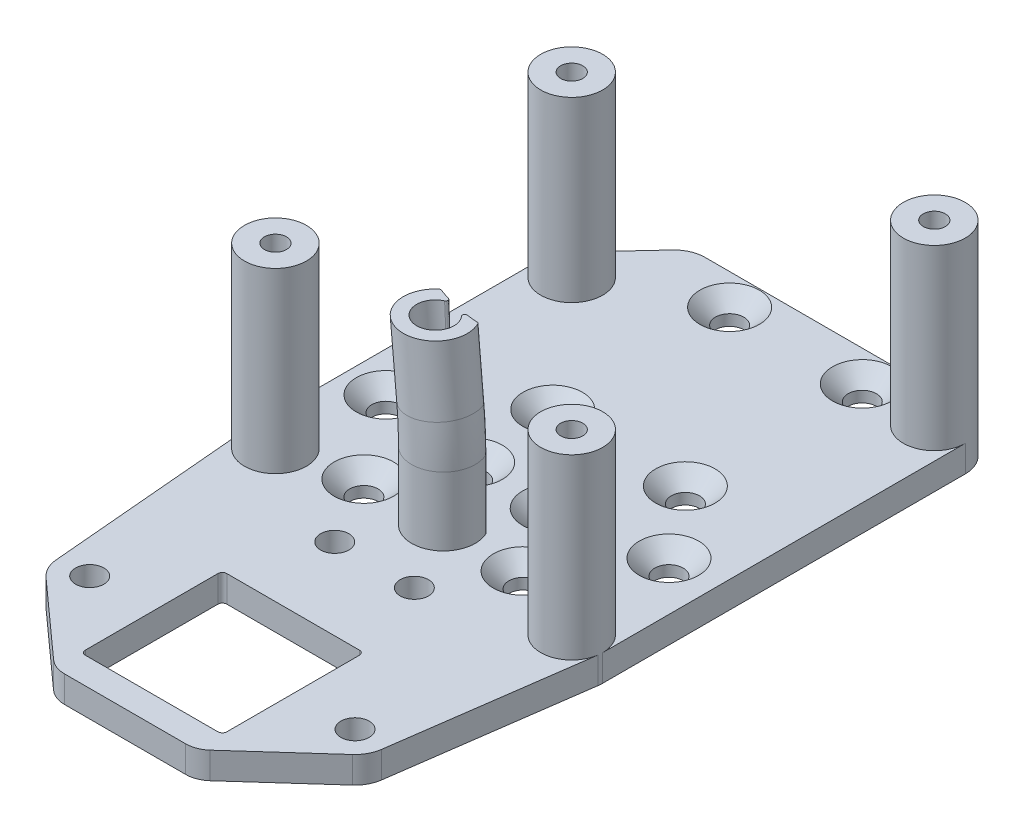
SolidWorks part; units mm, degrees
material "6061-T6 (SS)"
ref_plane "Front Plane" through (0, 0, 0) normal (0, 0, 1) x (1, 0, 0)
ref_plane "Top Plane" through (0, 0, 0) normal (0, 1, 0) x (1, 0, 0)
ref_plane "Right Plane" through (0, 0, 0) normal (1, 0, 0) x (0, 0, -1)
sketch "Hole Locations" plane through (0, 0, 0) normal (0, 1, 0) x (1, 0, 0)
  line L0 (0, 0) -> (0, 3.5) construction
  line L1 (0, 0) -> (0, 41) construction
  line L2 (0, 3.5) -> (-18, 3.5) construction
  line L3 (-14.64, 24.83) -> (-14.64, 23.33) construction
  line L4 (3.56, 24.83) -> (3.56, 23.33) construction
  line L5 (-32.84, 24.83) -> (-32.84, 23.33) construction
  circle A0 centre (-18, 3.5) radius 12.7 construction
  circle A1 centre (-18, 3.5) radius 9 construction
  arc A2 (3.56, 24.83) -> (-32.84, 24.83) centre (-14.64, 24.83) ccw construction
  arc A3 (-32.84, 23.33) -> (3.56, 23.33) centre (-14.64, 23.33) ccw construction
  point P3 (0, 41)
  point P8 (-35, 35)
  point P12 (-14.64, 24.08)
  point P17 (-35, 1.5)
  dimension "D5" = 25.4
  dimension "D6" = 18
  dimension "D10" = 18.2
  dimension "D11" = 35
  dimension "D2" = 3.5
  dimension "D3" = 41
  dimension "D4" = 18
  dimension "D7" = 3.36
  dimension "D8" = 20.58
  dimension "D9" = 1.5
  dimension "D12" = 1.5
  dimension "D13" = 35
sketch "Sketch2" plane through (0, 0, 0) normal (0, 1, 0) x (1, 0, 0)
  line L1 (-85.0501, -47.0767) -> (20.8074, -47.0767)
  line L2 (-85.0501, -47.0767) -> (-85.0501, 53.3551)
  line L3 (-85.0501, 53.3551) -> (20.8074, 53.3551)
  line L4 (20.8074, -47.0767) -> (20.8074, 53.3551)
extrude "Boss-Extrude1" add sketch "Sketch2" along normal blind 3
hole_wizard "Ø4.2 (4.2) Diameter Hole1" positions "Sketch5" profile "Sketch6" hole size "Ø4.2" standard "ANSI Metric" end condition up to next
sketch "Sketch5" plane through (0, 3, 0) normal (0, 1, 0) x (1, 0, 0)
  point P0 (-18, 3.5)
sketch "Sketch6" plane through (-18, 3, -3.5) normal (1, 0, 0) x (0, 0, 1)
  line L0 (0, 0) -> (0, 3)
  line L1 (0, 3) -> (2.1, 3)
  line L2 (2.1, 3) -> (2.1, 0)
  line L5 (2.1, 0) -> (0, 0)
  line L11 (0, -6.35) -> (0, 107.95) construction
  dimension "Thru Hole Dia." = 4.2
  dimension "Thru Hole Depth" = 3
sketch "Sketch7" plane through (0, 3, 0) normal (0, 1, 0) x (1, 0, 0)
  circle A0 centre (-35, 1.5) radius 3.5
  circle A1 centre (0, 41) radius 3.5
  circle A2 centre (0, 0) radius 3.5
  circle A3 centre (-35, 35) radius 3.5
  dimension "D1" = 7
extrude "Boss-Extrude2" add sketch "Sketch7" along normal blind 20.1
hole_wizard "Tap Drill for M3x0.5 Tap1" positions "Sketch8" profile "Sketch9" hole size "M3x0.5" standard "ANSI Metric" end condition up to next
sketch "Sketch8" plane through (0, 23.1, 0) normal (0, 1, 0) x (1, 0, 0)
  point P0 (-35, 1.5)
  point P3 (0, 41)
  point P6 (0, 0)
  point P9 (-35, 35)
sketch "Sketch9" plane through (-35, 23.1, -1.5) normal (1, 0, 0) x (0, 0, 1)
  line L0 (0, 0) -> (0, 23.1)
  line L1 (0, 23.1) -> (1.25, 23.1)
  line L2 (1.25, 23.1) -> (1.25, 0)
  line L5 (1.25, 0) -> (0, 0)
  line L11 (0, -6.35) -> (0, 107.95) construction
  dimension "Thru Hole Dia." = 2.5
  dimension "Thru Hole Depth" = 23.1
sketch "Chube Hole Positions" plane through (0, 3, 0) normal (0, 1, 0) x (1, 0, 0)
  line L0 (-18, 3.5) -> (-27, 3.5) construction
  circle A0 centre (-18, 3.5) radius 9 construction
  point P3 (-27, 3.5)
  point P4 (-22.5, 11.2942)
  point P7 (-13.5, 11.2942)
  point P8 (-9, 3.5)
  point P9 (-13.5, -4.2942)
  point P10 (-22.5, -4.2942)
  dimension "D3" = 9
  dimension "D2" = 6
hole_wizard "CSK for M3 SFHCS1" positions "Sketch15" profile "Sketch16" countersink size "M3" standard "ANSI Metric" end condition up to next
sketch "Sketch15" plane through (0, 3, 0) normal (0, 1, 0) x (1, 0, 0)
  point P24 (-22.5, 11.2942)
  point P27 (-13.5, 11.2942)
  point P30 (-9, 3.5)
  point P34 (-27, 3.5)
sketch "Sketch16" plane through (-22.5, 3, -11.2942) normal (1, 0, 0) x (0, 0, 1)
  line L0 (0, 0) -> (0, 3)
  line L1 (0, 3) -> (1.6, 3)
  line L2 (1.6, 3) -> (1.6, 1.76)
  line L3 (1.6, 1.76) -> (3.36, 0)
  line L5 (3.36, 0) -> (0, 0)
  line L6 (-1.6, 1.76) -> (-3.36, 0) construction
  line L11 (0, -6.35) -> (0, 107.95) construction
  dimension "Thru Hole Dia." = 3.2
  dimension "Thru Hole Depth" = 3
  dimension "Near C'Sink Dia." = 6.72
  dimension "Near C'Sink Angle" = 90
hole_wizard "M3 Clearance Hole1" positions "Sketch31" profile "Sketch32" hole size "M3" standard "ANSI Metric" end condition up to next
sketch "Sketch31" plane through (0, 3, 0) normal (0, 1, 0) x (1, 0, 0)
  circle A0 centre (-18, 3.5) radius 9 construction
  point P3 (-22.5, -4.2942)
  point P6 (-13.5, -4.2942)
sketch "Sketch32" plane through (-22.5, 3, 4.2942) normal (1, 0, 0) x (0, 0, 1)
  line L0 (0, 0) -> (0, 3)
  line L1 (0, 3) -> (1.6, 3)
  line L2 (1.6, 3) -> (1.6, 0)
  line L5 (1.6, 0) -> (0, 0)
  line L11 (0, -6.35) -> (0, 107.95) construction
  dimension "Thru Hole Dia." = 3.2
  dimension "Thru Hole Depth" = 3
sketch "MGN12 Hole Positions" plane through (0, 3, 0) normal (0, 1, 0) x (1, 0, 0)
  line L0 (-18, 3.5) -> (-13.29, 3.5) construction
  line L1 (0, 3.5) -> (-18, 3.5) construction
  line L2 (-15.645, 3.5) -> (-15.645, 31) construction
  line L4 (1.855, 17.5) -> (-33.145, 17.5)
  line L5 (1.855, 17.5) -> (1.855, 44.5)
  line L6 (1.855, 44.5) -> (-33.145, 44.5)
  line L7 (-33.145, 17.5) -> (-33.145, 44.5)
  line L8 (1.855, 17.5) -> (-33.145, 44.5) construction
  line L9 (1.855, 44.5) -> (-33.145, 17.5) construction
  line L10 (-8.145, 21) -> (-23.145, 21)
  line L11 (-8.145, 21) -> (-8.145, 41)
  line L12 (-8.145, 41) -> (-23.145, 41)
  line L13 (-23.145, 21) -> (-23.145, 41)
  line L14 (-8.145, 21) -> (-23.145, 41) construction
  line L15 (-8.145, 41) -> (-23.145, 21) construction
  circle A0 centre (0, 41) radius 3.5 construction
  dimension "D1" = 4.71
  dimension "D2" = 35
  dimension "D3" = 27
  dimension "D4" = 20
  dimension "D5" = 15
hole_wizard "CSK for M3 SFHCS2" positions "Sketch18" profile "Sketch19" countersink size "M3" standard "ANSI Metric" end condition up to next
sketch "Sketch18" plane through (0, 3, 0) normal (0, 1, 0) x (1, 0, 0)
  point P0 (-23.145, 41)
  point P3 (-8.145, 41)
  point P6 (-8.145, 21)
  point P9 (-23.145, 21)
sketch "Sketch19" plane through (-23.145, 3, -41) normal (1, 0, 0) x (0, 0, 1)
  line L0 (0, 0) -> (0, 3)
  line L1 (0, 3) -> (1.6, 3)
  line L2 (1.6, 3) -> (1.6, 1.76)
  line L3 (1.6, 1.76) -> (3.36, 0)
  line L5 (3.36, 0) -> (0, 0)
  line L6 (-1.6, 1.76) -> (-3.36, 0) construction
  line L11 (0, -6.35) -> (0, 107.95) construction
  dimension "Thru Hole Dia." = 3.2
  dimension "Thru Hole Depth" = 3
  dimension "Near C'Sink Dia." = 6.72
  dimension "Near C'Sink Angle" = 90
ref_plane "Plane1" through (0, 0, -3.5) normal (0, 0, 1) x (1, 0, 0)
sketch "Sketch20" plane through (0, 0, -3.5) normal (0, 0, 1) x (1, 0, 0)
  line L0 (-18, 3) -> (-18, 10.7231)
  line L2 (-18.2074, 15.2721) -> (-19.0139, 24.1)
  line L3 (-68, 10.7231) -> (-18.0519, 13) construction
  line L4 (-85.0501, 3) -> (20.8074, 3) construction
  line L6 (-31.5, 23.1) -> (-38.5, 23.1) construction
  arc A0 (-18, 10.7231) -> (-18.2074, 15.2721) centre (-68, 10.7231) ccw
  dimension "D1" = 10
  dimension "D2" = 50
  dimension "D3" = 95.22
  dimension "D4" = 1
sketch "Sketch26" plane through (0, 3, 0) normal (0, 1, 0) x (1, 0, 0)
  line L0 (-33, -21.5) -> (-3, -21.5) construction
  line L3 (-10, -29.5) -> (-26, -29.5)
  line L4 (-10, -29.5) -> (-10, -13.5)
  line L5 (-10, -13.5) -> (-26, -13.5)
  line L6 (-26, -29.5) -> (-26, -13.5)
  line L7 (-10, -29.5) -> (-26, -13.5) construction
  line L8 (-10, -13.5) -> (-26, -29.5) construction
  circle A0 centre (-18, -21.5) radius 8 construction
  circle A2 centre (-18, -21.5) radius 11 construction
  circle A3 centre (-33, -21.5) radius 3.5 construction
  circle A4 centre (-3, -21.5) radius 3.5 construction
  point P3 (-29, -21.5)
  point P5 (-18, 3.5)
  point P8 (-18, -21.5)
  dimension "D1" = 16
  dimension "D2" = 3
  dimension "D4" = 7
  dimension "D3" = 4
  dimension "D5" = 25
  dimension "D6" = 16
extrude "CPAP Hole" cut sketch "Sketch26" against normal up to surface (3 mm away) up to face at (-23.145, 0, -42.6)
hole_wizard "M3 Clearance Hole2" positions "Sketch27" profile "Sketch28" hole size "M3" standard "ANSI Metric" end condition up to next
sketch "Sketch27" plane through (0, 3, 0) normal (0, 1, 0) x (1, 0, 0)
  point P0 (-3, -21.5)
  point P14 (-33, -21.5)
sketch "Sketch28" plane through (-3, 3, 21.5) normal (1, 0, 0) x (0, 0, 1)
  line L0 (0, 0) -> (0, 3)
  line L1 (0, 3) -> (1.6, 3)
  line L2 (1.6, 3) -> (1.6, 0)
  line L5 (1.6, 0) -> (0, 0)
  line L11 (0, -6.35) -> (0, 107.95) construction
  dimension "Thru Hole Dia." = 3.2
  dimension "Thru Hole Depth" = 3
sketch "Sketch21" plane through (0, 3, 0) normal (0, 1, 0) x (1, 0, 0)
  circle A0 centre (-18, 3.5) radius 2.1 construction
  circle A1 centre (-18, 3.5) radius 2.1
  circle A2 centre (-18, 3.5) radius 3.6
  dimension "D1" = 1.5
sweep "Sweep1" add profiles "Sketch21" path "Sketch20"
sketch "Sketch23" plane through (0, 0, 47.0767) normal (0, 0, 1) x (1, 0, 0)
  line L1 (-38.5, 23.1) -> (3.5, 23.1)
  line L2 (-38.5, 23.1) -> (-38.5, 24.4275)
  line L3 (-38.5, 24.4275) -> (3.5, 24.4275)
  line L4 (3.5, 23.1) -> (3.5, 24.4275)
extrude "Cut-Extrude1" cut sketch "Sketch23" against normal through all
sketch "Sketch25" plane through (0, 3, 0) normal (0, 1, 0) x (1, 0, 0)
  line L0 (-14.64, 24.83) -> (-14.64, 23.33) construction
  line L1 (3.56, 24.83) -> (3.56, 23.33)
  line L2 (-32.84, 24.83) -> (-32.84, 23.33)
  arc A0 (3.56, 24.83) -> (-32.84, 24.83) centre (-14.64, 24.83) ccw
  arc A1 (-32.84, 23.33) -> (3.56, 23.33) centre (-14.64, 23.33) ccw
  circle A2 centre (-18, 3.5) radius 3.6 construction
  point P2 (-14.64, 24.08)
  dimension "D1" = 20.58
  dimension "D3" = 18.2
  dimension "D2" = 3.36
  dimension "D4" = 1.5
extrude "Cut-Extrude3" cut sketch "Sketch25" along normal up to surface (20.1 mm away) up to face at (-22.5375, 23.1, -3.5)
fillet "Fillet1" radius 0.25 12 edges at (-20.6472, 15.195, -6.15) (-17.5822, 18.9453, -5.3694) (-16.8679, 11.266, -5.2669) (-18.729, 19.4348, -5.5953) (-18.579, 14.9229, -5.5614) (-14.7905, 6.8616, -5.1306) (-20.4932, 6.8616, -6.0969) (-16.8644, 6.8616, -5.2664) (-18.4904, 6.8616, -5.5419)
sketch "Sketch29" plane through (0, 3, 0) normal (0, 1, 0) x (1, 0, 0)
  line L3 (3.5, 0) -> (3.5, 41)
  line L4 (0, 44.5) -> (-29.4219, 44.5)
  line L5 (-31.9852, 43.3831) -> (-37.5633, 37.3831)
  line L13 (-38.5, 35) -> (-38.5, 1.5)
  line L16 (-10, -32.5) -> (-26, -32.5)
  line L21 (-10, -32.5) -> (-26, -32.5)
  line L22 (-36.4868, -21.8032) -> (-38.4868, 1.1968)
  line L23 (-26, -32.5) -> (-35.34, -24.1027)
  line L24 (0.4664, -21.9837) -> (3.4664, -0.4837)
  line L25 (-10, -32.5) -> (-0.66, -24.1027)
  circle A0 centre (-33, -21.5) radius 3.5 construction
  arc A1 (-36.4868, -21.8032) -> (-35.34, -24.1027) centre (-33, -21.5) ccw
  circle A2 centre (-35, 1.5) radius 3.5 construction
  arc A3 (-38.5, 1.5) -> (-38.4868, 1.1968) centre (-35, 1.5) ccw
  circle A4 centre (-35, 35) radius 3.5 construction
  circle A5 centre (0, 0) radius 3.5 construction
  circle A6 centre (0, 41) radius 3.5 construction
  arc A12 (3.4664, -0.4837) -> (3.5, 0) centre (0, 0) ccw
  arc A13 (3.5, 41) -> (0, 44.5) centre (0, 41) ccw
  arc A14 (-29.4219, 44.5) -> (-31.9852, 43.3831) centre (-29.4219, 41) ccw
  circle A15 centre (-35, 35) radius 3.5 construction
  arc A17 (-0.66, -24.1027) -> (0.4664, -21.9837) centre (-3, -21.5) ccw
  arc A20 (-37.5633, 37.3831) -> (-38.5, 35) centre (-35, 35) ccw
  dimension "D2" = 3.5
  dimension "D1" = 5.5781
  dimension "D3" = 3
extrude "Cut-Extrude5" cut sketch "Sketch29" against normal up to surface (3 mm away) flip side to cut up to face at (-3, 0, 19.9)
fillet "Fillet2" radius 3 2 edges at (-10, 1.5, 32.5) (-26, 1.5, 32.5)
fillet "Fillet3" radius 0.5 4 edges at (-26, 1.5, 29.5) (-10, 1.5, 13.5) (-10, 1.5, 29.5) (-26, 1.5, 13.5)
hole_wizard "CSK for M3 SFHCS3" positions "Sketch35" profile "Sketch36" countersink size "M3" standard "ANSI Metric" end condition up to next
sketch "Sketch35" plane through (0, 3, 0) normal (0, 1, 0) x (1, 0, 0)
  line L0 (-34, 13) -> (-2, 13) construction
  point P0 (-34, 13)
  point P2 (-2, 13)
  point P10 (-18, 13)
  dimension "D1" = 32
  dimension "D2" = 9.5
sketch "Sketch36" plane through (-34, 3, -13) normal (1, 0, 0) x (0, 0, 1)
  line L0 (0, 0) -> (0, 3)
  line L1 (0, 3) -> (1.6, 3)
  line L2 (1.6, 3) -> (1.6, 1.76)
  line L3 (1.6, 1.76) -> (3.36, 0)
  line L5 (3.36, 0) -> (0, 0)
  line L6 (-1.6, 1.76) -> (-3.36, 0) construction
  line L11 (0, -6.35) -> (0, 107.95) construction
  dimension "Thru Hole Dia." = 3.2
  dimension "Thru Hole Depth" = 3
  dimension "Near C'Sink Dia." = 6.72
  dimension "Near C'Sink Angle" = 90
